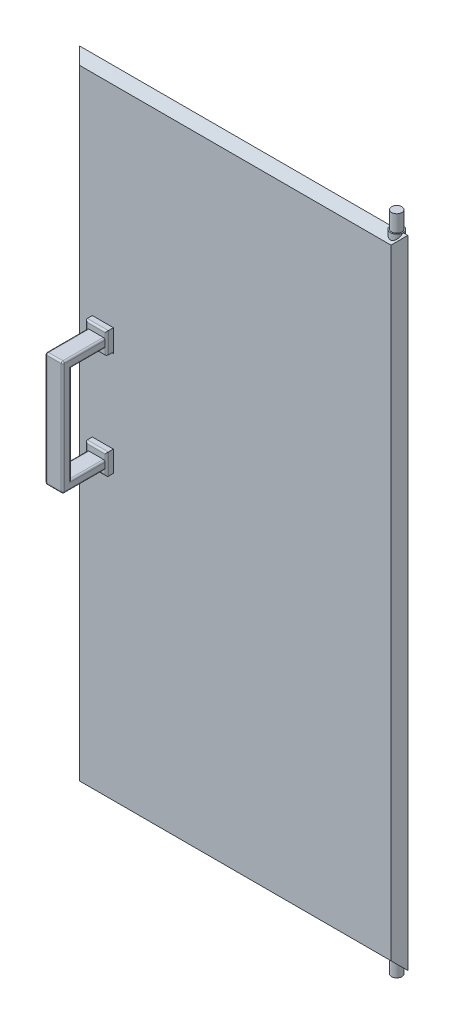
SolidWorks part; units mm, degrees
ref_plane "Front Plane" through (0, 0, 0) normal (0, 0, 1) x (1, 0, 0)
ref_plane "Top Plane" through (0, 0, 0) normal (0, 1, 0) x (1, 0, 0)
ref_plane "Right Plane" through (0, 0, 0) normal (1, 0, 0) x (0, 0, -1)
sketch "Sketch1" plane through (0, 0, 0) normal (0, 0, 1) x (1, 0, 0)
  line L0 (-47.1094, 19.5562) -> (342.8906, 19.5562)
  line L1 (342.8906, 19.5562) -> (342.8906, -737.2438)
  line L2 (342.8906, -737.2438) -> (-47.1094, -737.2438)
  line L3 (-47.1094, -737.2438) -> (-47.1094, 19.5562)
extrude "Boss-Extrude1" add sketch "Sketch1" along normal blind 20
sketch "Sketch2" plane through (0, 19.5562, 0) normal (0, 1, 0) x (1, 0, 0)
  circle A0 centre (329.7783, -10) radius 6.05
extrude "Boss-Extrude2" add sketch "Sketch2" along normal blind 10
sketch "Sketch3" plane through (0, -737.2438, 0) normal (0, -1, 0) x (1, 0, 0)
  circle A0 centre (329.7783, 10) radius 6.05
extrude "Boss-Extrude3" add sketch "Sketch3" along normal blind 10
chamfer "Chamfer1" distance 10 angle 45 8 edges at (147.8906, -737.2438, 0) (-47.1094, -358.8438, 0) (147.8906, 19.5562, 0) (342.8906, -358.8438, 0) (147.8906, -737.2438, 20) (-47.1094, -358.8438, 20) (147.8906, 19.5562, 20) (342.8906, -358.8438, 20)
sketch "Sketch4" plane through (0, 0, 20) normal (0, 0, 1) x (1, 0, 0)
  line L0 (-37.1094, 9.5562) -> (-37.1094, -358.8438)
  line L1 (-37.1094, 9.5562) -> (-37.1094, -727.2438) construction
  line L3 (12.8906, -358.8438) -> (12.8906, -258.8438)
  line L4 (12.8906, -258.8438) -> (-37.1094, -258.8438)
  line L5 (-37.1094, -258.8438) -> (-37.1094, -458.8438)
  line L6 (-37.1094, -458.8438) -> (12.8906, -458.8438)
  line L7 (12.8906, -458.8438) -> (12.8906, -358.8438)
extrude "Boss-Extrude4" add sketch "Sketch4" along normal blind 50 contours L6 L7 L3 L4 L0 region at (-12.1094, -358.8438, 20)
sketch "Sketch5" plane through (-37.1094, 0, 0) normal (-1, 0, 0) x (0, 0, 1)
  line L0 (20, -258.8438) -> (20, -278.8438)
  line L1 (20, -258.8438) -> (20, -458.8438) construction
  line L2 (20, -278.8438) -> (50, -278.8438)
  line L3 (50, -278.8438) -> (50, -438.8438)
  line L4 (50, -438.8438) -> (20, -438.8438)
  line L5 (20, -438.8438) -> (20, -278.8438)
  line M1 (20, -258.8438) -> (20, -458.8438)
extrude "Cut-Extrude1" cut sketch "Sketch5" against normal blind 131 contours L4 L3 L2 M1 region at (-37.1094, -358.8438, 35)
chamfer "Chamfer2" distance 10 angle 45 8 edges at (-37.1094, -358.8438, 70) (-37.1094, -458.8438, 45) (-12.1094, -458.8438, 70) (12.8906, -458.8438, 45) (12.8906, -358.8438, 70) (12.8906, -258.8438, 45) (-12.1094, -258.8438, 70) (-37.1094, -258.8438, 45)
sketch "Sketch6" plane through (0, 0, 20) normal (0, 0, 1) x (1, 0, 0)
  line L0 (-37.1094, -268.8438) -> (-27.1094, -258.8438)
  line L1 (-27.1094, -258.8438) -> (2.8906, -258.8438) construction
  line L2 (-27.1094, -258.8438) -> (2.8906, -258.8438)
  line L3 (2.8906, -258.8438) -> (12.8906, -268.8438)
  line L4 (12.8906, -268.8438) -> (12.8906, -448.8438)
  line L5 (12.8906, -448.8438) -> (2.8906, -458.8438)
  line L6 (2.8906, -458.8438) -> (-27.1094, -458.8438)
  line L7 (-27.1094, -458.8438) -> (-37.1094, -448.8438)
  line L8 (-37.1094, -448.8438) -> (-37.1094, -268.8438)
extrude "Cut-Extrude2" cut sketch "Sketch6" along normal blind 78
sketch "Sketch7" plane through (0, 0, 20) normal (0, 0, 1) x (1, 0, 0)
  line L0 (332.8906, 9.5562) -> (-37.1094, 9.5562) construction
  line L1 (-22.1094, -240.4438) -> (2.8906, -240.4438)
  line L2 (-22.1094, -240.4438) -> (-22.1094, -265.4438)
  line L3 (-22.1094, -265.4438) -> (2.8906, -265.4438)
  line L4 (2.8906, -240.4438) -> (2.8906, -265.4438)
  line L5 (-22.1094, -365.4438) -> (2.8906, -365.4438)
  line L6 (-22.1094, -365.4438) -> (-22.1094, -390.4438)
  line L7 (-22.1094, -390.4438) -> (2.8906, -390.4438)
  line L8 (2.8906, -365.4438) -> (2.8906, -390.4438)
  line L9 (-37.1094, 9.5562) -> (-37.1094, -727.2438) construction
  dimension "D1" = 250
  dimension "D2" = 15
  dimension "D3" = 25
  dimension "D4" = 25
  dimension "D5" = 25
  dimension "D6" = 25
  dimension "D7" = 15
  dimension "D8" = 100
extrude "Boss-Extrude5" add sketch "Sketch7" along normal blind 8
fillet "Fillet1" radius 2 4 edges at (-9.6094, -265.4438, 20) (-22.1094, -252.9438, 28) (2.8906, -252.9438, 28) (-9.6094, -240.4438, 28)
fillet "Fillet2" radius 2 4 edges at (2.8906, -377.9438, 28) (-9.6094, -390.4438, 28) (-22.1094, -377.9438, 28) (-9.6094, -365.4438, 28)
sketch "Sketch8" plane through (0, 0, 28) normal (0, 0, 1) x (1, 0, 0)
  line L0 (-20.1094, -242.4438) -> (-20.1094, -265.4438) construction
  line L1 (-20.1094, -248.4256) -> (0.8906, -248.4256)
  line L2 (-20.1094, -248.4256) -> (-20.1094, -258.9173)
  line L3 (-20.1094, -258.9173) -> (0.8906, -258.9173)
  line L4 (0.8906, -248.4256) -> (0.8906, -258.9173)
  line L5 (0.8906, -265.4438) -> (0.8906, -242.4438) construction
  line L6 (-20.1094, -367.4438) -> (-20.1094, -388.4438) construction
  line L7 (-20.1094, -373.9986) -> (0.8906, -373.9986)
  line L8 (-20.1094, -373.9986) -> (-20.1094, -384.1625)
  line L9 (-20.1094, -384.1625) -> (0.8906, -384.1625)
  line L10 (0.8906, -373.9986) -> (0.8906, -384.1625)
  line L11 (0.8906, -388.4438) -> (0.8906, -367.4438) construction
extrude "Boss-Extrude6" add sketch "Sketch8" along normal blind 40
sketch "Sketch9" plane through (0, 0, 68) normal (0, 0, 1) x (1, 0, 0)
  line L1 (-20.1094, -248.4256) -> (0.8906, -248.4256)
  line L2 (-20.1094, -248.4256) -> (-20.1094, -384.1625)
  line L3 (-20.1094, -384.1625) -> (0.8906, -384.1625)
  line L4 (0.8906, -248.4256) -> (0.8906, -384.1625)
extrude "Boss-Extrude7" add sketch "Sketch9" along normal blind 10
fillet "Fillet3" radius 2 4 edges at (0.8906, -316.458, 68) (-20.1094, -316.458, 68) (0.8906, -316.294, 78) (-20.1094, -316.294, 78)
fillet "Fillet4" radius 2 14 edges at (0.3048, -248.4256, 77.4142) (-9.6094, -248.4256, 78) (-19.5236, -248.4256, 77.4142) (0.3048, -384.1625, 77.4142) (-19.5236, -384.1625, 77.4142) (0.8906, -258.9173, 49) (0.8906, -248.4256, 52) (-20.1094, -248.4256, 52) (-20.1094, -258.9173, 49) (0.8906, -373.9986, 49) (-20.1094, -373.9986, 49) (-9.6094, -384.1625, 78) (0.8906, -384.1625, 52) (-20.1094, -384.1625, 52)
sketch "Sketch15" plane through (0, 29.5562, 0) normal (0, 1, 0) x (1, 0, 0)
  circle A0 centre (329.7783, -10) radius 7.5
  dimension "D1" = 15
extrude "Boss-Extrude17" add sketch "Sketch15" against normal blind 20
sketch "Sketch17" plane through (0, 29.5562, 0) normal (0, 1, 0) x (1, 0, 0)
  circle A0 centre (329.7783, -10) radius 7.5
extrude "Cut-Extrude7" cut sketch "Sketch17" against normal blind 10
sketch "Sketch18" plane through (0, 19.5562, 0) normal (0, 1, 0) x (1, 0, 0)
  circle A0 centre (329.7783, -10) radius 6.05
  dimension "D1" = 12.1
extrude "Boss-Extrude18" add sketch "Sketch18" along normal blind 20
